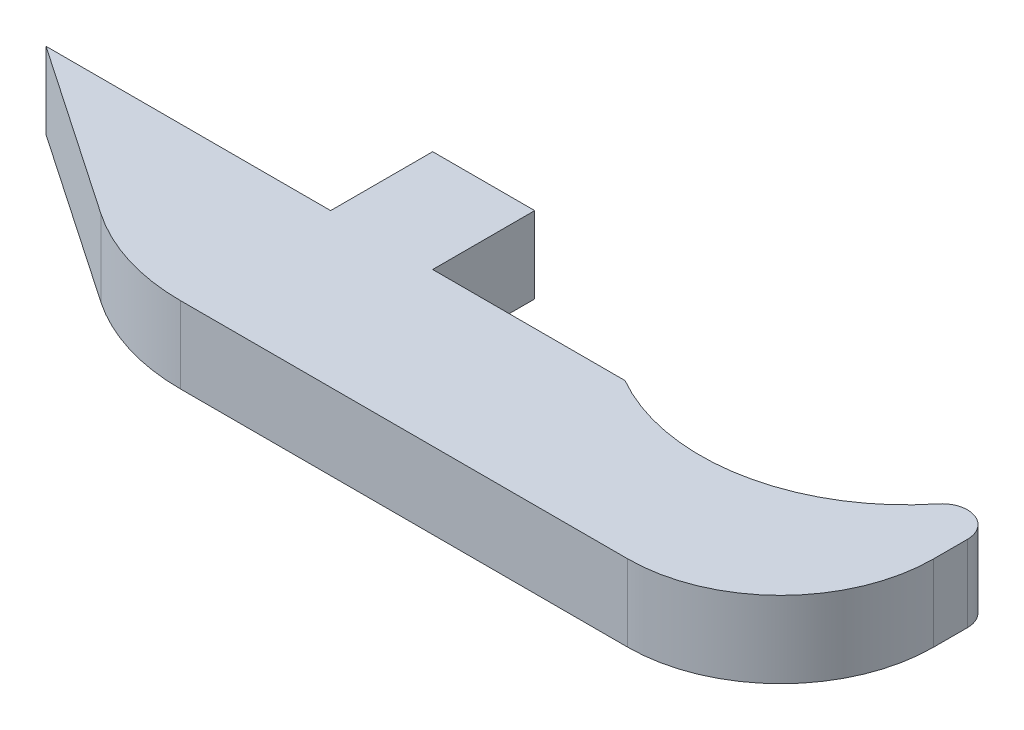
SolidWorks part; units mm, degrees
material "AISI 4130 Steel, annealed at 865C"
ref_plane "X-Y Datum" through (0, 0, 0) normal (0, 0, 1) x (1, 0, 0)
ref_plane "X-Z Datum" through (0, 0, 0) normal (0, 1, 0) x (1, 0, 0)
ref_plane "Y-Z Datum" through (0, 0, 0) normal (1, 0, 0) x (0, 0, -1)
sketch "Sketch1" plane through (0, 0, 0) normal (0, 1, 0) x (1, 0, 0)
  line L0 (20.5085, 0) -> (0, 0) construction
  line L1 (45.593, 0) -> (0, 0)
  line L2 (45.593, 0) -> (45.593, 11.1252)
  line L3 (17.145, -9.525) -> (58.42, -9.525)
  line L4 (58.42, 11.1252) -> (58.42, -9.525)
  line L5 (3.175, 0) -> (17.145, -9.525)
  circle A0 centre (45.593, 11.1252) radius 12.827
  dimension "D3" = 25.654
  dimension "D5" = 9.525
  dimension "D1" = 45.593
  dimension "D2" = 11.1252
  dimension "D4" = 3.175
  dimension "D6" = 41.275
extrude "Boss-Extrude1" add sketch "Sketch1" along normal blind 4.7625 contours L1 A0 region at (34.7653, 0, 4.3342)
fillet "Fillet1" radius 9.525 1 edges at (58.42, 2.3813, 9.525)
fillet "Fillet2" radius 1.5875 1 edges at (58.42, 2.3813, -11.1252)
fillet "Fillet4" radius 12.7 1 edges at (17.145, 2.3813, 9.525)
sketch "Sketch2" plane through (0, 0, 0) normal (0, -1, 0) x (1, 0, 0)
  line L1 (27.2395, -6.35) -> (27.2395, 0)
  line L2 (-7.0505, -6.35) -> (27.8745, -6.35) construction
  line L3 (27.2395, 0) -> (20.8895, 0)
  line L4 (27.2395, 0) -> (27.2395, -6.35)
  line L5 (27.2395, -6.35) -> (20.8895, -6.35)
  line L6 (20.8895, 0) -> (20.8895, -6.35)
  line L7 (33.5895, 0) -> (33.5895, -6.35) construction
  line M6 (3.175, 0) -> (39.2085, 0)
  dimension "D1" = 6.35
  dimension "D2" = 6.35
extrude "Boss-Extrude2" add sketch "Sketch2" against normal blind 4.7625 contours L6 L5 L1 M6 region at (24.0645, 0, -3.175)
